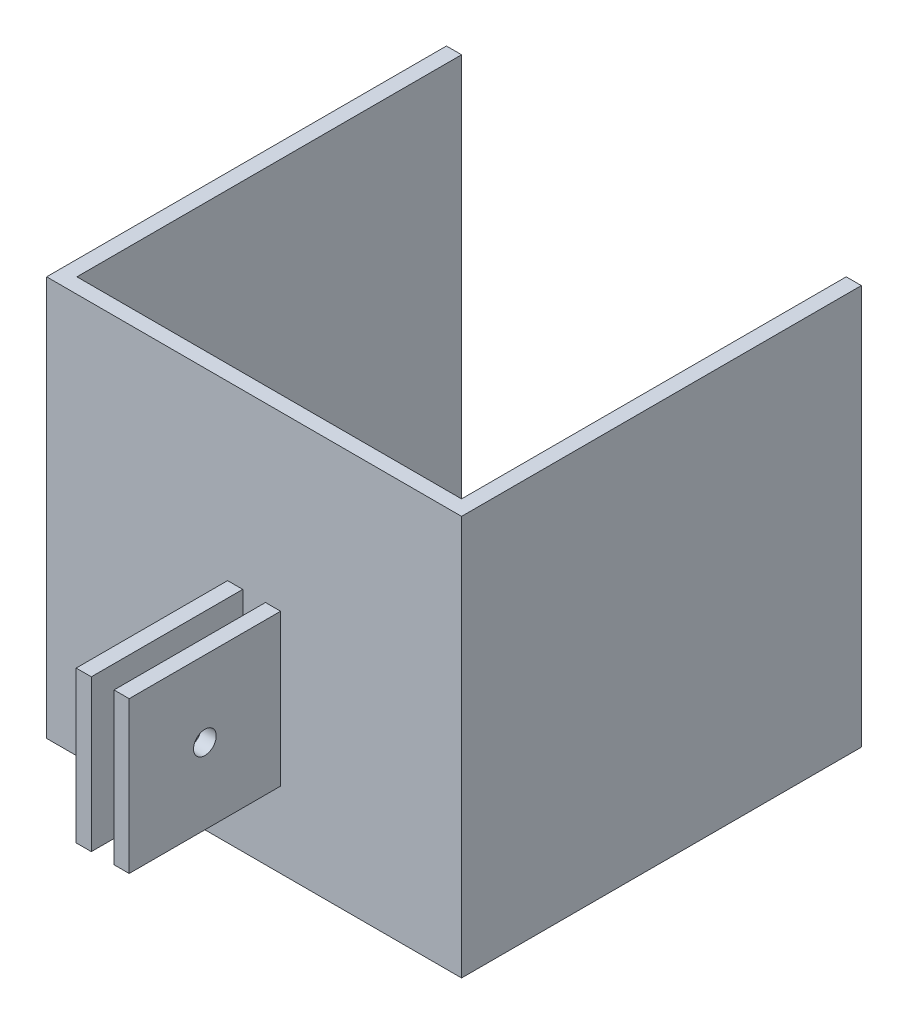
SolidWorks part; units mm, degrees
ref_plane "Front Plane" through (0, 0, 0) normal (0, 0, 1) x (1, 0, 0)
ref_plane "Top Plane" through (0, 0, 0) normal (0, 1, 0) x (1, 0, 0)
ref_plane "Right Plane" through (0, 0, 0) normal (1, 0, 0) x (0, 0, -1)
sketch "Sketch1" plane through (0, 0, 0) normal (0, 1, 0) x (1, 0, 0)
  line L0 (0, 50.8) -> (-2, 50.8)
  line L1 (0, 0) -> (50.8, 0)
  line L2 (0, 0) -> (0, 50.8)
  line L3 (0, 50.8) -> (50.8, 50.8)
  line L4 (50.8, 0) -> (50.8, 50.8)
  line L5 (-2, 50.8) -> (-2, -2)
  line L6 (-2, -2) -> (52.8, -2)
  line L7 (52.8, -2) -> (52.8, 50.8)
  line L8 (52.8, 50.8) -> (50.8, 50.8)
  line L9 (21.9, -2) -> (21.9, -22)
  line L10 (21.9, -22) -> (28.9, -22)
  line L11 (28.9, -22) -> (28.9, -2)
  line L12 (26.9, -22) -> (26.9, -2)
  line L13 (23.9, -22) -> (23.9, -2)
  point P18 (25.4, -2)
  point P19 (25.4, -22)
  point P20 (0, 0)
  point P21 (0, 0)
  dimension "D1" = 50.8
  dimension "D2" = 50.8
  dimension "D3" = 2
  dimension "D4" = 2
  dimension "D5" = 2
  dimension "D6" = 7
  dimension "D7" = 3
  dimension "D8" = 20
  dimension "D9" = 1.5
extrude "Boss-Extrude1" add sketch "Sketch1" along normal blind 2 contours L7 L8 L4 L1 L2 L0 L5 L6 | L1 L4 L3 L2 region at (-0.761, 0, -25.4) region at (25.4, 0, -25.4)
extrude "Boss-Extrude2" add sketch "Sketch1<3>" along normal blind 50.8 from surface contours L7 L8 L4 L1 L2 L0 L5 L6 region at (-0.761, 0, -25.4) starting at face at (25.4, 2, -24.4)
sketch "Sketch1<3>" plane through (0, 0, 0) normal (0, 1, 0) x (1, 0, 0) same geometry as "Sketch1"
extrude "Boss-Extrude3" add sketch "Sketch1<4>" along normal blind 10 and the other way blind 10 from offset 20 contours L12 L10 L11 L6 | L10 L13 L6 L9 region at (22.9, 0, 12) region at (27.9, 0, 12)
sketch "Sketch1<4>" plane through (0, 0, 0) normal (0, 1, 0) x (1, 0, 0) same geometry as "Sketch1"
sketch "Sketch3" plane through (28.9, 0, 0) normal (1, 0, 0) x (0, 0, -1)
  line L0 (-22, 30) -> (-2, 10) construction
  circle A0 centre (-12, 20) radius 1.5
  dimension "D1" = 3
extrude "Cut-Extrude1" cut sketch "Sketch3" against normal up to surface (7 mm away) up to face at (21.9, 20, 12)
